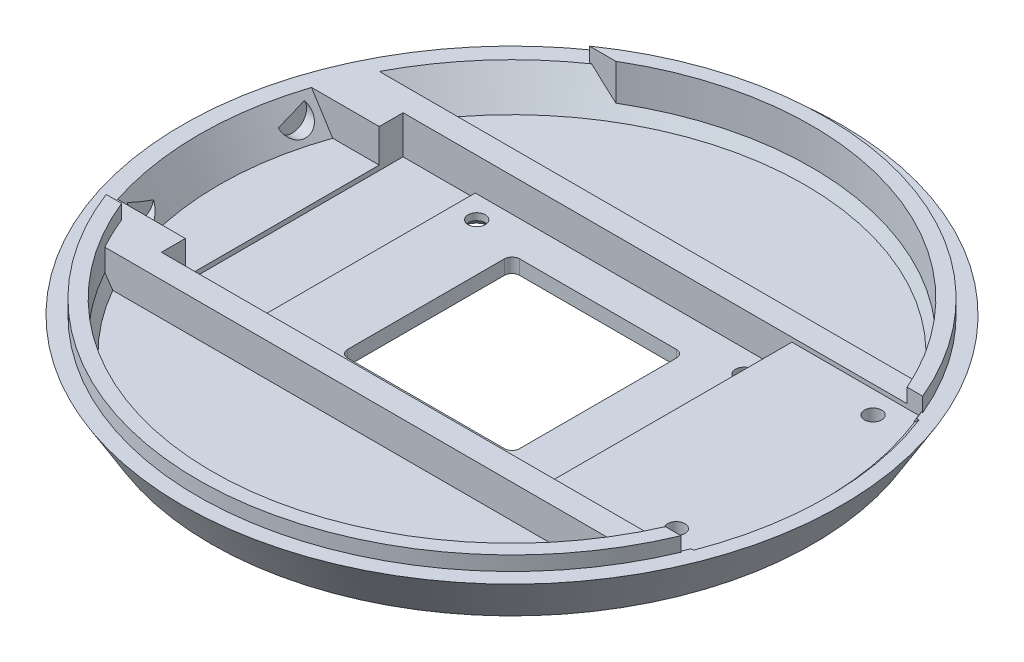
SolidWorks part; units mm, degrees
ref_plane "Front Plane" through (0, 0, 0) normal (0, 0, 1) x (1, 0, 0)
ref_plane "Top Plane" through (0, 0, 0) normal (0, 1, 0) x (1, 0, 0)
ref_plane "Right Plane" through (0, 0, 0) normal (1, 0, 0) x (0, 0, -1)
sketch "Sketch1" plane through (0, 0, 0) normal (0, 0, 1) x (1, 0, 0)
  line L0 (0, 0) -> (63, 0)
  line L1 (63, 0) -> (69, 10)
  line L6 (0, 3) -> (61.3014, 3)
  line L7 (61.3014, 3) -> (65.5014, 10)
  line L8 (69, 10) -> (65.5014, 10)
  line L9 (0, 0) -> (0, 3)
  line L10 (61.3014, 3) -> (66.4275, 11.5435) construction
  dimension "D1" = 69
  dimension "D2" = 63
  dimension "D3" = 10
  dimension "D4" = 3
revolve "Revolve1" add sketch "Sketch1" angle 360 about L9
sketch "Sketch2" plane through (0, 3, 0) normal (0, 1, 0) x (1, 0, 0)
  line L1 (-18, 18) -> (18, 18)
  line L2 (-18, 18) -> (-18, -18)
  line L3 (-18, -18) -> (18, -18)
  line L4 (18, 18) -> (18, -18)
  line L5 (-18, 18) -> (18, -18) construction
  line L6 (-18, -18) -> (18, 18) construction
  point P0 (0, 0)
  dimension "D1" = 36
  dimension "D2" = 36
  dimension "D12" = 0
  dimension "D13" = 0
extrude "Cut-Extrude1" cut sketch "Sketch2" against normal through all
fillet "Fillet1" radius 1.6 4 edges at (18, 1.5, -18) (18, 1.5, 18) (-18, 1.5, 18) (-18, 1.5, -18)
hole_wizard "CSK for M3 Countersunk Flat Head Screw2" positions "3DSketch3" profile "Sketch6" countersink size "M3" standard "ISO" end condition through all
sketch3d "3DSketch3"
  line L0 (16.4, 0, -18) -> (-16.4, 0, -18) construction
  line L1 (-16.4, 0, 18) -> (16.4, 0, 18) construction
  line L2 (18, 0, 16.4) -> (18, 0, -16.4) construction
  line L3 (-18, 0, -16.4) -> (-18, 0, 16.4) construction
  point P0 (-28, 0, -20.6)
  point P2 (-28, 0, 20.6)
  point P4 (28, 0, 20.6)
  point P6 (28, 0, -20.6)
  dimension "D1" = 2.6
  dimension "D2" = 2.6
  dimension "D3" = 2.6
  dimension "D4" = 2.6
  dimension "D5" = 10
  dimension "D6" = 10
  dimension "D7" = 10
  dimension "D8" = 10
sketch "Sketch6" plane through (-28, 0, -20.6) normal (1, 0, 0) x (0, 0, -1)
  line L0 (0, 0) -> (0, 10)
  line L1 (0, 10) -> (1.8, 10)
  line L2 (1.8, 10) -> (1.8, 1.55)
  line L3 (1.8, 1.55) -> (3.35, 0)
  line L5 (3.35, 0) -> (0, 0)
  line L6 (-1.8, 1.55) -> (-3.35, 0) construction
  line L11 (0, -6.35) -> (0, 107.95) construction
  dimension "Thru Hole Dia." = 3.6
  dimension "Thru Hole Depth" = 10
  dimension "Near C'Sink Dia." = 6.7
  dimension "Near C'Sink Angle" = 90
sketch "Sketch19" plane through (0, 3, 0) normal (0, 1, 0) x (1, 0, 0)
  line L0 (-33, 25) -> (-33, -25) construction
  line L1 (-48.1, 25.3) -> (-33, 25.3)
  line L2 (-48.1, 25.3) -> (-48.1, -25.3)
  line L3 (-48.1, -25.3) -> (-33, -25.3)
  line L4 (-33, 25.3) -> (-33, -25.3)
  line L5 (-47.8, 45.1467) -> (-47.8, -23.3) construction
  line L6 (-33.3, 25) -> (-47.8, 25) construction
  line L7 (-33.3, -25) -> (-47.8, -25) construction
  dimension "D1" = 0.3
  dimension "D2" = 0.3
  dimension "D3" = 0.3
extrude "Cut-Extrude4" cut sketch "Sketch19" against normal blind 1
sketch "Sketch21" plane through (0, 0, 0) normal (1, 0, 0) x (0, 0, -1)
  line L3 (-25.3, 3) -> (25.3, 3)
  line L6 (25.3, 3) -> (25.3, 9.1)
  line L7 (25.3, 9.1) -> (-25.3, 9.1)
  line L8 (-25.3, 9.1) -> (-25.3, 3)
  dimension "D1" = 0
  dimension "D2" = 0.3
  dimension "D3" = 0.3
  dimension "D4" = 0
extrude "Boss-Extrude1" add sketch "Sketch21" along normal up to next from offset 33.3
sketch "Sketch22" plane through (0, 0, 0) normal (1, 0, 0) x (0, 0, -1)
  line L0 (65.5014, 10) -> (-65.5014, 10) construction
  line L1 (-30.3, 10) -> (-25.3, 10)
  line L2 (-30.3, 10) -> (-30.3, 3)
  line L3 (-30.3, 3) -> (-25.3, 3)
  line L4 (-25.3, 10) -> (-25.3, 3)
  line L5 (25.3, 10) -> (30.3, 10)
  line L6 (25.3, 10) -> (25.3, 3)
  line L7 (25.3, 3) -> (30.3, 3)
  line L8 (30.3, 10) -> (30.3, 3)
  dimension "D1" = 0
  dimension "D2" = 0
  dimension "D3" = 5
  dimension "D4" = 5
  dimension "D5" = 0
  dimension "D6" = 0
  dimension "D7" = 0
  dimension "D8" = 0
extrude "Boss-Extrude2" add sketch "Sketch22" along normal up to next and the other way up to next
sketch "Sketch23" plane through (0, 0, 0) normal (1, 0, 0) x (0, 0, -1)
  line L0 (20, 39) -> (20, 7) construction
  line L1 (25.3, 10) -> (20.3, 10)
  line L2 (25.3, 10) -> (25.3, 3)
  line L3 (25.3, 3) -> (20.3, 3)
  line L4 (20.3, 10) -> (20.3, 3)
  line L5 (-25.3, 10) -> (-20.3, 10)
  line L6 (-25.3, 10) -> (-25.3, 3)
  line L7 (-25.3, 3) -> (-20.3, 3)
  line L8 (-20.3, 10) -> (-20.3, 3)
  line L9 (-20, 7) -> (-20, 39) construction
  dimension "D1" = 0.3
  dimension "D2" = 0.3
  dimension "D3" = 0
  dimension "D4" = 0
  dimension "D5" = 0
  dimension "D6" = 0
  dimension "D7" = 0
  dimension "D8" = 0
extrude "Boss-Extrude3" add sketch "Sketch23" against normal up to next from offset 48.1 offset against normal yes
sketch "Sketch24" plane through (0, 10, 0) normal (0, 1, 0) x (1, 0, 0)
  line L0 (-32.1302, 53.9) -> (-37.6544, 53.9)
  line L1 (57.4236, -25.3) -> (60.6875, -25.3)
  line L2 (-58.1429, -23.6) -> (-61.3686, -23.6)
  line L3 (-61.7504, -23.3) -> (-58.1, -23.3) construction
  line L4 (57.4236, 25.3) -> (60.6875, 25.3)
  line L7 (60.8117, -25) -> (-47.8, -25) construction
  line L8 (-47.8, 25) -> (60.8117, 25) construction
  arc A0 (-61.3686, -23.6) -> (60.6875, -25.3) centre (0, 0) ccw
  arc A1 (-58.1429, -23.6) -> (57.4236, -25.3) centre (0, 0) ccw
  arc A2 (57.4236, 25.3) -> (-32.1302, 53.9) centre (0, 0) ccw
  arc A3 (60.6875, 25.3) -> (-37.6544, 53.9) centre (0, 0) ccw
  dimension "D1" = 131.5
  dimension "D2" = 125.5
  dimension "D3" = 0.3
  dimension "D4" = 0
  dimension "D5" = 0.3
  dimension "D6" = 0.3
extrude "Boss-Extrude4" add sketch "Sketch24" along normal blind 3 and the other way up to next
sketch "Sketch25" plane through (0, 10, 0) normal (0, 1, 0) x (1, 0, 0)
  line L0 (61.6364, 23.6) -> (60, 23.6)
  line L1 (60, 23.6) -> (60, -23.6)
  line L2 (60, -23.6) -> (61.6364, -23.6)
  line L3 (61.4831, 23.3) -> (22.3682, 23.3) construction
  line L4 (-47.8, -23.3) -> (61.4831, -23.3) construction
  arc A0 (61.6364, -23.6) -> (61.6364, 23.6) centre (0, 0) ccw
  dimension "D1" = 132
  dimension "D2" = 0.3
  dimension "D3" = 0.3
  dimension "D4" = 60
extrude "Cut-Extrude5" cut sketch "Sketch25" against normal blind 0.9
chamfer "Chamfer1" distance 0.9 angle 45 1 edges at (66, 9.1, 0)
sketch "Sketch26" plane through (0, 0, 0) normal (1, 0, 0) x (0, 0, -1)
  circle A2 centre (-16, 7) radius 3
  circle A3 centre (16, 7) radius 3
  dimension "D3" = 6
  dimension "D1" = 16
  dimension "D4" = 6
  dimension "D2" = 16
extrude "Cut-Extrude6" cut sketch "Sketch26" against normal blind 4 from offset 58 offset against normal yes
hole_wizard "CSK for M3 Countersunk Flat Head Screw3" positions "Sketch27" profile "Sketch28" countersink size "M3" standard "ISO" end condition through all
sketch "Sketch27" plane through (0, 0, 0) normal (0, -1, 0) x (-1, 0, 0)
  line L0 (16.4, -18) -> (-16.4, -18) construction
  line L1 (-16.4, 18) -> (16.4, 18) construction
  line L2 (-18, -16.4) -> (-18, 16.4) construction
  point P0 (-55, 20.6)
  point P2 (-55, -20.6)
  dimension "D1" = 2.6
  dimension "D2" = 2.6
  dimension "D3" = 37
  dimension "D4" = 37
sketch "Sketch28" plane through (55, 0, -20.6) normal (1, 0, 0) x (0, 0, -1)
  line L0 (0, 0) -> (0, 13)
  line L1 (0, 13) -> (1.8, 13)
  line L2 (1.8, 13) -> (1.8, 1.55)
  line L3 (1.8, 1.55) -> (3.35, 0)
  line L5 (3.35, 0) -> (0, 0)
  line L6 (-1.8, 1.55) -> (-3.35, 0) construction
  line L11 (0, -6.35) -> (0, 107.95) construction
  dimension "Thru Hole Dia." = 3.6
  dimension "Thru Hole Depth" = 13
  dimension "Near C'Sink Dia." = 6.7
  dimension "Near C'Sink Angle" = 90
